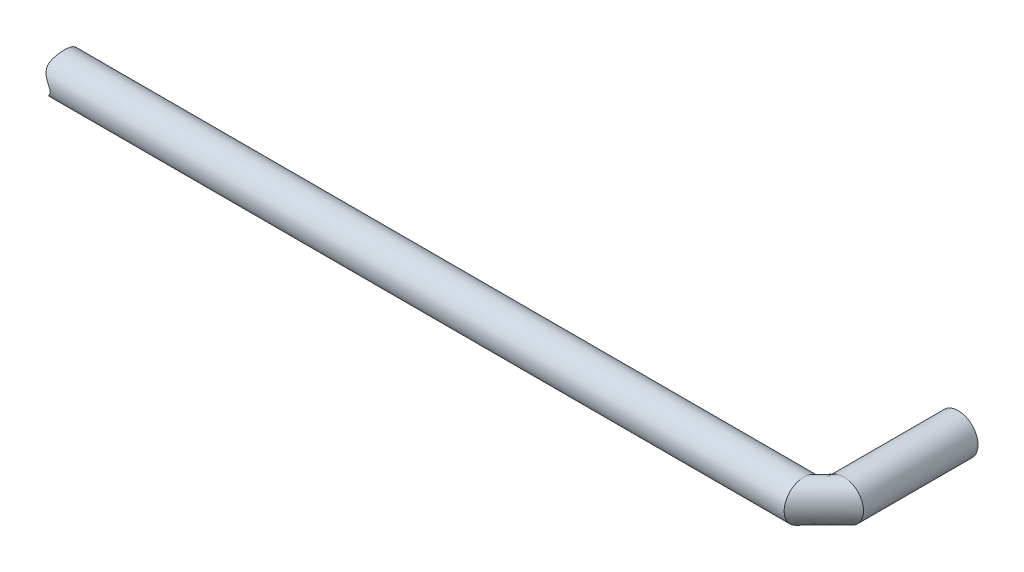
SolidWorks part; units mm, degrees
ref_plane "Front Plane" through (0, 0, 0) normal (0, 0, 1) x (1, 0, 0)
ref_plane "Top Plane" through (0, 0, 0) normal (0, 1, 0) x (1, 0, 0)
ref_plane "Right Plane" through (0, 0, 0) normal (1, 0, 0) x (0, 0, -1)
sketch "Sketch1" plane through (0, 0, 0) normal (0, 0, 1) x (1, 0, 0)
  circle A0 centre (0, 0) radius 6.35
  circle A1 centre (0, 0) radius 4.826
extrude "Boss-Extrude1" add sketch "Sketch1" along normal blind 17.78 contours A0 | A1
sketch "Sketch37" plane through (0, 0, 0) normal (1, 0, 0) x (0, 0, -1)
  circle A0 centre (-24.2367, 0) radius 6.35
  circle A1 centre (-24.2367, 0) radius 4.826
extrude "Boss-Extrude2" add sketch "Sketch37" against normal blind 254 separate body
sketch "Sketch38" plane through (0, 0, 0) normal (1, 0, 0) x (0, 0, -1)
  circle A0 centre (-24.2367, 0) radius 6.35
  circle A1 centre (-24.2367, 0) radius 4.826
extrude "Cut-Extrude1" cut sketch "Sketch38" against normal blind 6.35
loft "Loft1" add section edge at (-6.35, 0, 19.4107) section edge at (4.826, 0, 17.78) connector at (-6.35, -0.3726, 19.4251) connector at (-4.7388, -0.9132, 17.78)
loft "Loft2" add section edge at (-6.35, 0, 17.8867) section edge at (6.35, 0, 17.78) connector at (-6.35, 3.3145, 29.6531) connector at (5.8262, 2.5255, 17.78)
sketch "Sketch39" plane through (0, 0, 0) normal (0, 0, -1) x (-1, 0, 0)
  circle A0 centre (0, 0) radius 4.826
  circle A1 centre (0, 0) radius 6.35
extrude "Boss-Extrude3" add sketch "Sketch39" along normal blind 19.05
sketch "Sketch40" plane through (0, 0, 0) normal (0, 0, 1) x (1, 0, 0)
  spline S0 degree 3 poles (-278.1451, 22.5473) (-234.8684, 15.9387) (-246.8524, 4.1096) (-240.3118, -1.3583) (-246.1119, -4.7744) (-245.277, -8.7548) (-244.7563, -16.5946) (-268.6948, -12.4949) (-278.1451, 22.5473) (-234.8684, 15.9387) (-246.8524, 4.1096) knots -0.735859 -0.566529 -0.27155 0 0.072474 0.134819 0.192028 0.229339 0.264141 0.433471 0.72845 1 1.072474 1.134819 1.192028 only from (-242.2235, 9.8572) to (-242.2235, 9.8572)
extrude "Cut-Extrude2" cut sketch "Sketch40" along normal blind 87.63
